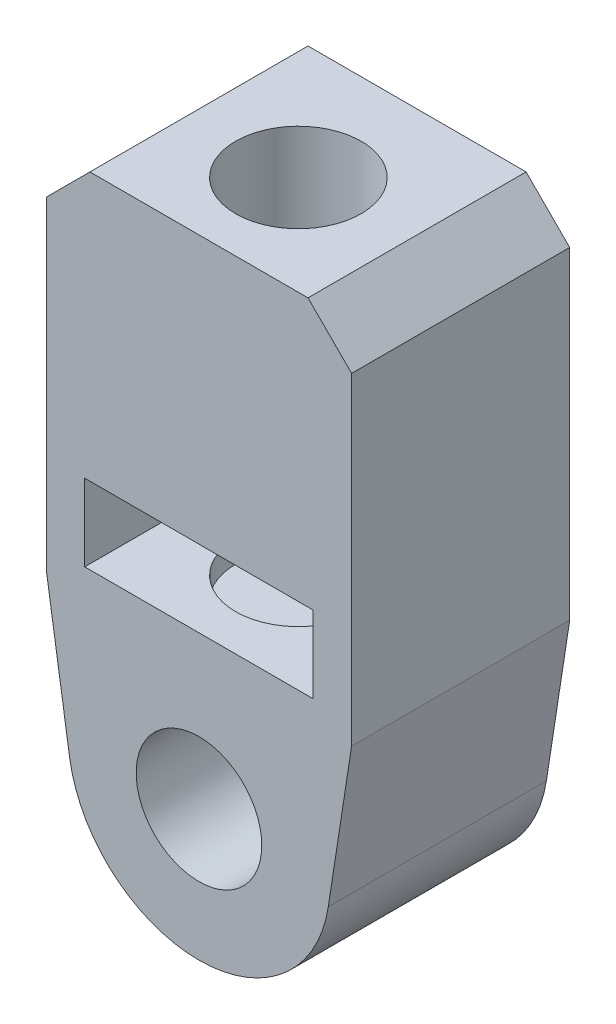
SolidWorks part; units mm, degrees
ref_plane "Front Plane" through (0, 0, 0) normal (0, 0, 1) x (1, 0, 0)
ref_plane "Top Plane" through (0, 0, 0) normal (0, 1, 0) x (1, 0, 0)
ref_plane "Right Plane" through (0, 0, 0) normal (1, 0, 0) x (0, 0, -1)
sketch "Sketch1" plane through (0, 0, 0) normal (0, 0, 1) x (1, 0, 0)
  line L0 (-5.5562, 4.7625) -> (-5.5562, 18.0975)
  line L1 (-5.5562, 18.0975) -> (5.5562, 18.0975)
  line L2 (5.5562, 18.0975) -> (5.5562, 4.7625)
  line L3 (-5.5562, 4.7625) -> (-4.7065, -0.7284)
  line L4 (4.7065, -0.7284) -> (5.5562, 4.7625)
  circle A1 centre (0, 0) radius 2.286
  arc A2 (-4.7065, -0.7284) -> (4.7065, -0.7284) centre (0, 0) ccw
  point P10 (0, 18.0975)
  dimension "D1" = 9.525
  dimension "D2" = 4.572
  dimension "D3" = 13.335
  dimension "D4" = 11.1125
  dimension "D5" = 4.7625
extrude "Boss-Extrude1" add sketch "Sketch1" along normal up to surface (7.9375 mm away)
sketch "Sketch2" plane through (0, 18.0975, 0) normal (0, 1, 0) x (1, 0, 0)
  circle A1 centre (0, -4.3187) radius 2.286
  circle A2 centre (0, -4.3187) radius 1.7525 construction
  dimension "D1" = 4.572
extrude "Cut-Extrude1" cut sketch "Sketch2" against normal offset from surface (13.335 mm away) 4.7625 up to plane "Top Plane"
sketch "Sketch3" plane through (0, 4.7625, 0) normal (0, 1, 0) x (1, 0, 0)
  line L11 (5.5562, -7.9375) -> (-5.5562, -7.9375) construction
  line L12 (-1.9064, -1.0167) -> (-4.1565, -4.9141)
  line L16 (4.1565, -4.9141) -> (1.9064, -1.0167)
  line L17 (1.9064, -1.0167) -> (-1.9064, -1.0167)
  line L18 (-4.1565, -4.9141) -> (-4.1565, -7.9375)
  line L19 (-4.1565, -7.9375) -> (4.1565, -7.9375)
  line L20 (4.1565, -7.9375) -> (4.1565, -4.9141)
  line L22 (-1.9064, -7.6207) -> (0, -7.6207) [skipped]
  line L23 (-3.8128, -4.3187) -> (-2.8596, -5.9697) [skipped]
  line L24 (2.1818, -7.1437) -> (2.8596, -5.9697) [skipped]
  circle A0 centre (0, -4.3187) radius 3.302 construction
  dimension "D1" = 6.604
extrude "Cut-Extrude2" cut sketch "Sketch3" along normal blind 2.794 from offset 0.7937
chamfer "Chamfer1" distance 1.5875 angle 45 2 edges at (5.5562, 18.0975, 3.9688) (-5.5562, 18.0975, 3.9688)
